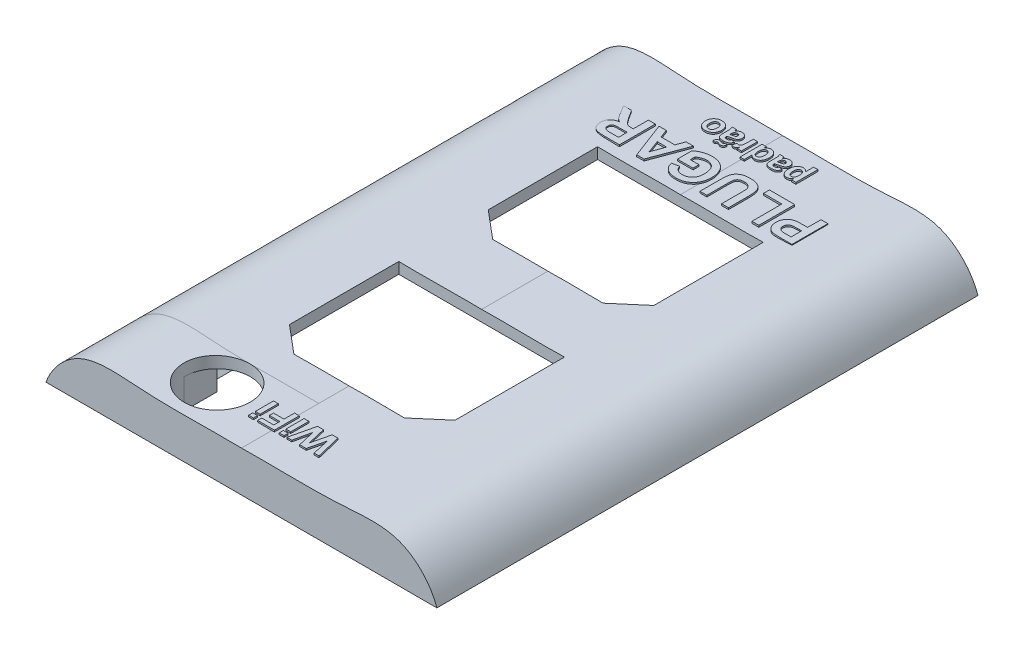
SolidWorks part; units mm, degrees
ref_plane "Plano frontal" through (0, 0, 0) normal (0, 0, 1) x (1, 0, 0)
ref_plane "Plano superior" through (0, 0, 0) normal (0, 1, 0) x (1, 0, 0)
ref_plane "Plano direito" through (0, 0, 0) normal (1, 0, 0) x (0, 0, -1)
sketch "Forma Principal" plane through (0, 0, 0) normal (0, 0, 1) x (1, 0, 0)
  line L0 (20.4, -12.0302) -> (20.4, -9.6302)
  line L1 (0, 6.1527) -> (0, -15) construction
  line L2 (-20.4, -15) -> (-18.9151, -13.5151)
  line L3 (-35.4, -15) -> (-20.4, -15)
  line L4 (-20.4, -9.6302) -> (20.4, -9.6302)
  line L5 (-18.9151, -13.5151) -> (-20.4, -12.0302)
  line L6 (-20.4, -12.0302) -> (-20.4, -9.6302)
  line L7 (18.9151, -13.5151) -> (20.4, -12.0302)
  line L8 (35.4, -15) -> (20.4, -15)
  line L9 (20.4, -15) -> (18.9151, -13.5151)
  spline S0 degree 3 poles (-35.4, -15) (-34.3652, -12.0385) (-29.3659, -6.48) (-20.6106, -7.4076) (-11.0454, -7.778) (-4.641, -7.544) (0, -7.6302) knots 0 0 0 0 0.248558 0.508028 0.637571 1 1 1 1
  spline S1 degree 3 poles (35.4, -15) (34.3652, -12.0385) (29.3659, -6.48) (20.6106, -7.4076) (11.0454, -7.778) (4.641, -7.544) (0, -7.6302) knots 0 0 0 0 0.248558 0.508028 0.637571 1 1 1 1
  point P0 (0, 0)
  point P25 (0, -9.6302)
  dimension "D6" = 10
  dimension "D7" = 19
  dimension "D9" = 4
  dimension "D10" = 2
  dimension "D12" = 2.2
  dimension "D13" = 2
  dimension "D8" = 14
  dimension "D3" = 38.793
  dimension "D2" = 20.4
  dimension "D4" = 4
  dimension "D5" = 15
  dimension "D11" = 2
  dimension "D14" = 2.1
  dimension "D15" = 2.1
  dimension "D16" = 45
  dimension "D17" = 15
  dimension "D18" = 7
  dimension "D19" = 2.4
extrude "Corpo da Tampa" add sketch "Forma Principal" along normal blind 84
sketch "Esboço4" plane through (0, 0, 84) normal (0, 0, 1) x (1, 0, 0)
  line L1 (0, -7.6302) -> (0, -15) construction
  line L2 (-35.4, -15) -> (35.4, -15)
  spline S0 degree 3 poles (-35.4, -15) (-34.3652, -12.0385) (-29.3659, -6.48) (-20.6106, -7.4076) (-11.0454, -7.778) (-4.641, -7.544) (0, -7.6302) knots 0 0 0 0 0.248558 0.508028 0.637571 1 1 1 1
  spline S1 degree 3 poles (35.4, -15) (34.3652, -12.0385) (29.3659, -6.48) (20.6106, -7.4076) (11.0454, -7.778) (4.641, -7.544) (0, -7.6302) knots 0 0 0 0 0.248558 0.508028 0.637571 1 1 1 1
  dimension "D7" = 4
  dimension "D6" = 38.793
  dimension "D2" = 7.3698
  dimension "D3" = 7.3698
  dimension "D4" = 7.5698
  dimension "D5" = 6.8931
  dimension "D8" = 10
  dimension "D9" = 4
  dimension "D10" = 7.3698
  dimension "D14" = 7
  dimension "D18" = 7
extrude "Tampa Superior" add sketch "Esboço4" along normal blind 14
sketch "Esboço6" plane through (20.4, 0, 0) normal (-1, 0, 0) x (0, 0, 1)
  line L0 (84, -12.0302) -> (0, -12.0302) construction
  line L1 (17.75, -12.0302) -> (16.25, -12.0302)
  line L2 (17.75, -12.0302) -> (17.75, -15)
  line L3 (17.75, -15) -> (16.25, -15)
  line L4 (16.25, -12.0302) -> (16.25, -15)
  line L8 (13, -12.0302) -> (0, -12.0302)
  line L9 (13, -12.0302) -> (13, -15)
  line L10 (13, -15) -> (0, -15)
  line L11 (0, -12.0302) -> (0, -15)
  line L12 (84, -15) -> (0, -15) construction
  dimension "D1" = 1.5
  dimension "D2" = 16.25
  dimension "D3" = 13
extrude "Gancho Tampa" cut sketch "Esboço6" along normal blind 1.5 draft 45 draft outward yes
sketch "Esboço Antena" plane through (0, -15, 0) normal (0, -1, 0) x (1, 0, 0)
  line L3 (-6.4, 90) -> (-6.4, 84)
  line L4 (-20.4, 84) -> (20.4, 84) construction
  line L5 (-6.4, 84) -> (-18.4, 84)
  line L6 (-18.4, 84) -> (-18.4, 90)
  line L8 (-20.4, 84) -> (-20.4, 0) construction
  arc A0 (-6.4, 90) -> (-18.4, 90) centre (-12.4, 90) ccw
  dimension "D1" = 6
  dimension "D2" = 6
  dimension "D3" = 8
sketch "Furo" plane through (0, -9.6302, 0) normal (0, -1, 0) x (1, 0, 0)
  line L0 (0, 82) -> (0, 0) construction
  line L2 (-15, 38.3045) -> (-10, 42.5)
  line L3 (-10, 42.5) -> (10, 42.5)
  line L4 (-15, 38.3045) -> (-15, 18.5)
  line L5 (-15, 18.5) -> (15, 18.5)
  line L6 (15, 38.3045) -> (15, 18.5)
  line L7 (-15, 42.5) -> (15, 18.5) construction
  line L8 (-15, 18.5) -> (15, 42.5) construction
  line L9 (10, 42.5) -> (15, 38.3045)
  line L11 (-20.4, 0) -> (20.4, 0) construction
  point P5 (0, 30.5)
  dimension "D1" = 18.5
  dimension "D2" = 24
  dimension "D3" = 30
  dimension "D4" = 5
  dimension "D5" = 40
  dimension "D6" = 5
  dimension "D7" = 40
extrude "Furo Furo" cut sketch "Furo" against normal blind 10
mirror "Gancho Espelho" about plane through (0, 0, 0) normal (1, 0, 0) of "Gancho Tampa"
pattern_linear "Furo Copia" count 2 spacing 36 along (0, 0, 1) of "Furo Furo"
extrude "Furo Interno Antena" cut sketch "Esboço Antena" against normal up to surface (5.3698 mm away) up to face at (0, -9.6302, 69.1015)
sketch "Furo Antena" plane through (0, -9.6302, 0) normal (0, -1, 0) x (1, 0, 0)
  circle A0 centre (-12.4, 90) radius 6
extrude "Corte Antena" cut sketch "Furo Antena" against normal through all
sketch "Escrito" plane through (0, -9.6302, 0) normal (0, -1, 0) x (1, 0, 0)
  line L0 (-20.4, 10) -> (20.4, 10) construction
  line L1 (-20.4, 84) -> (-20.4, 0) construction
  line L2 (20.4, 84) -> (20.4, 0) construction
  line L3 (-20.4, 0) -> (20.4, 0) construction
  line L4 (-20.4, 3.5) -> (20.4, 3.5) construction
  line L5 (20.4, 0) -> (20.4, 13) construction
  line L6 (-6.4, 84) -> (20.4, 84) construction
  line L7 (-20.4, 0) -> (-20.4, 13) construction
  line L8 (20.4, 88) -> (-4.6, 88) construction
  line L10 (20.4, 84) -> (20.4, 17.75) construction
  text T0 "PLUGAR" font "Arial" height 6.5
  text T1 "padrão" font "Arial" height 4
  text T2 "WiFi" font "Arial" height 4.5
  dimension "D1" = 10
  dimension "D2" = 3.5
  dimension "D3" = 0.9059
  dimension "D4" = 10.7726
  dimension "D5" = 3.5
  dimension "D6" = 20.4
  dimension "D7" = 25
  dimension "D8" = 0.7452
  dimension "D9" = 17.2307
  dimension "D10" = 4
extrude "Texto" add sketch "Escrito" against normal blind 2.3
